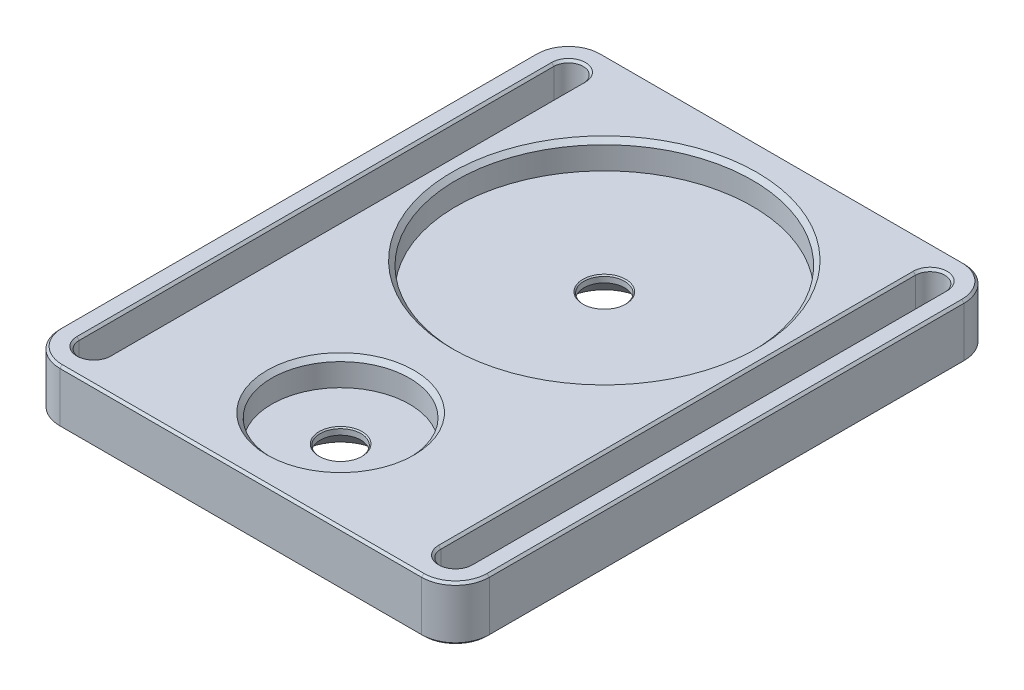
SolidWorks part; units mm, degrees
material "6061-T6 Aluminum"
ref_plane "Front Plane" through (0, 0, 0) normal (0, 0, 1) x (1, 0, 0)
ref_plane "Top Plane" through (0, 0, 0) normal (0, 1, 0) x (1, 0, 0)
ref_plane "Right Plane" through (0, 0, 0) normal (1, 0, 0) x (0, 0, -1)
sketch "Sketch1" plane through (0, 0, 0) normal (0, 1, 0) x (1, 0, 0)
  line L0 (0, 39.58) -> (0, 32.75) construction
  line L1 (-40, -80.42) -> (40, -80.42)
  line L2 (-47.5, -72.92) -> (-47.5, 32.08)
  line L3 (-40, 39.58) -> (40, 39.58)
  line L4 (47.5, -72.92) -> (47.5, 32.08)
  line L5 (0, -73.59) -> (0, -80.42) construction
  line L6 (-40, 32.08) -> (-40, -72.92) construction
  line L7 (-36.75, 32.08) -> (-36.75, -72.92)
  line L8 (-43.25, 32.08) -> (-43.25, -72.92)
  line L9 (40, 32.08) -> (40, -72.92) construction
  line L10 (43.25, 32.08) -> (43.25, -72.92)
  line L11 (36.75, 32.08) -> (36.75, -72.92)
  line L12 (-40, 0) -> (0, 0) construction
  line L13 (0, 0) -> (40, 0) construction
  line L14 (-40, -72.92) -> (-40, 32.08) construction
  line L15 (-46, -72.92) -> (-46, 32.08)
  line L16 (-34, -72.92) -> (-34, 32.08)
  line L17 (40, -72.92) -> (40, 32.08) construction
  line L18 (34, -72.92) -> (34, 32.08)
  line L19 (46, -72.92) -> (46, 32.08)
  circle A0 centre (0, 0) radius 32.75
  circle A1 centre (0, -58.34) radius 15.25
  arc A3 (-36.75, 32.08) -> (-43.25, 32.08) centre (-40, 32.08) ccw
  arc A4 (-43.25, -72.92) -> (-36.75, -72.92) centre (-40, -72.92) ccw
  arc A5 (43.25, 32.08) -> (36.75, 32.08) centre (40, 32.08) ccw
  arc A6 (36.75, -72.92) -> (43.25, -72.92) centre (40, -72.92) ccw
  circle A7 centre (0, 0) radius 4.25
  circle A8 centre (0, -58.34) radius 4.25
  arc A9 (-40, 39.58) -> (-47.5, 32.08) centre (-40, 32.08) ccw
  arc A11 (47.5, 32.08) -> (40, 39.58) centre (40, 32.08) ccw
  arc A12 (-47.5, -72.92) -> (-40, -80.42) centre (-40, -72.92) ccw
  arc A13 (40, -80.42) -> (47.5, -72.92) centre (40, -72.92) ccw
  arc A14 (-46, -72.92) -> (-34, -72.92) centre (-40, -72.92) ccw
  arc A15 (-34, 32.08) -> (-46, 32.08) centre (-40, 32.08) ccw
  arc A16 (34, -72.92) -> (46, -72.92) centre (40, -72.92) ccw
  arc A17 (46, 32.08) -> (34, 32.08) centre (40, 32.08) ccw
  point P0 (0, 0)
  point P2 (-40, -20.42)
  point P17 (-40, -20.42)
  point P22 (40, -20.42)
  point P46 (40, -20.42)
  dimension "D1" = 30.5
  dimension "D2" = 65.5
  dimension "D5" = 8.5
  dimension "D3" = 58.34
  dimension "D4" = 6.5
  dimension "D6" = 80
  dimension "D7" = 12
  dimension "D8" = 95
  dimension "D9" = 120
extrude "Boss-Extrude1" add sketch "Sketch1" along normal blind 12 contours L1 A13 L4 A11 L3 A9 L2 A12 A17 L19 A16 L18 A15 L16 A14 L15 A0 A1 | A0 A7 | A1 A8 | L11 A6 L10 A5 | L16 A15 L15 A14 A4 L8 A3 L7 | L19 A17 L18 A16 A6 L11 A5 L10 | L8 A4 L7 A3 | A7 | A8 region at (-45.1951, 0, 78.1151) region at (-40, 0, 20.42) region at (40, 0, 20.42) region at (-44.8239, 0, 20.42) region at (35.1761, 0, 20.42) region at (-31.8237, 0, 0) region at (-14.8187, 0, 58.34) region at (0, 0, 0) region at (0, 0, 58.34)
extrude "Cut-Extrude2" cut sketch "Sketch1<4>" along normal through all contours L11 A6 L10 A5 | A7 | A8 | L8 A4 L7 A3 region at (-40, 0, 20.42) region at (40, 0, 20.42) region at (0, 0, 0) region at (0, 0, 58.34)
sketch "Sketch1<4>" plane through (0, 0, 0) normal (0, 1, 0) x (1, 0, 0) same geometry as "Sketch1"
extrude "Cut-Extrude3" cut sketch "Sketch1<6>" along normal through all from offset 6 contours A0 A7 | A1 A8 region at (-31.8237, 0, 0) region at (-14.8187, 0, 58.34)
sketch "Sketch1<6>" plane through (0, 0, 0) normal (0, 1, 0) x (1, 0, 0) same geometry as "Sketch1"
chamfer "Chamfer1" distance 1 angle 45 2 edges at (0, 12, 73.59) (0, 12, 32.75)
chamfer "Chamfer2" distance 0.5 angle 45 36 edges at (0, 6, 62.59) (0, 0, 62.59) (0, 6, 4.25) (0, 0, 4.25) (43.25, 12, 20.42) (40, 12, -35.33) (40, 12, 76.17) (36.75, 12, 20.42) (43.25, 0, 20.42) (40, 0, -35.33) (40, 0, 76.17) (36.75, 0, 20.42) (-36.75, 12, 20.42) (-40, 12, -35.33) (-40, 12, 76.17) (-43.25, 12, 20.42) (-36.75, 0, 20.42) (-40, 0, -35.33) (-40, 0, 76.17) (-43.25, 0, 20.42) (0, 12, -39.58) (-45.3033, 12, -37.3833) (45.3033, 12, -37.3833) (-47.5, 12, 20.42) (47.5, 12, 20.42) (-45.3033, 12, 78.2233) (45.3033, 12, 78.2233) (0, 12, 80.42) (0, 0, -39.58) (-45.3033, 0, -37.3833) (45.3033, 0, -37.3833) (-47.5, 0, 20.42) (47.5, 0, 20.42) (-45.3033, 0, 78.2233) (45.3033, 0, 78.2233) (0, 0, 80.42)
hole_wizard "CSK for M8 Flat Head Machine Screw1" positions "Sketch2" profile "Sketch3" countersink size "M8" standard "ANSI Metric" end condition through all
sketch "Sketch2" plane through (0, 0, 0) normal (0, -1, 0) x (-1, 0, 0)
  point P0 (0, 0)
  point P3 (0, -58.34)
sketch "Sketch3" plane through (0, 0, 0) normal (1, 0, 0) x (0, 0, -1)
  line L0 (0, 0) -> (0, 12)
  line L1 (0, 12) -> (4.5, 12)
  line L2 (4.5, 12) -> (4.5, 4.5)
  line L3 (4.5, 4.5) -> (9, 0)
  line L5 (9, 0) -> (0, 0)
  line L6 (-4.5, 4.5) -> (-9, 0) construction
  line L11 (0, -6.35) -> (0, 107.95) construction
  dimension "Thru Hole Dia." = 9
  dimension "Thru Hole Depth" = 12
  dimension "Near C'Sink Dia." = 18
  dimension "Near C'Sink Angle" = 90
